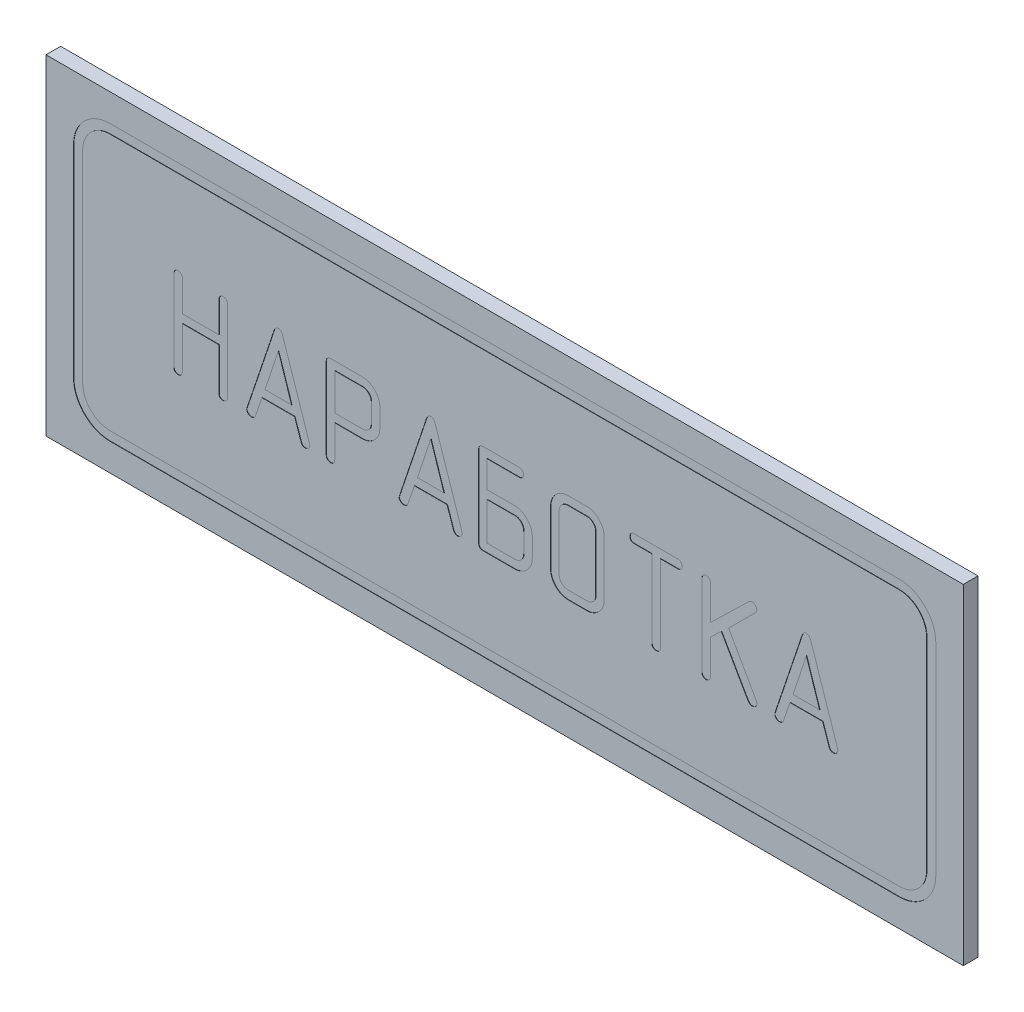
SolidWorks part; units mm, degrees
ref_plane "Спереди" through (0, 0, 0) normal (0, 0, 1) x (1, 0, 0)
ref_plane "Сверху" through (0, 0, 0) normal (0, 1, 0) x (1, 0, 0)
ref_plane "Справа" through (0, 0, 0) normal (1, 0, 0) x (0, 0, -1)
sketch "Эскиз1" plane through (0, 0, 0) normal (0, 0, 1) x (1, 0, 0)
  line L1 (0, 0) -> (50, 0)
  line L2 (0, 0) -> (0, 18)
  line L3 (0, 18) -> (50, 18)
  line L4 (50, 0) -> (50, 18)
  dimension "D1" = 50
  dimension "D2" = 18
extrude "Вытянуть1" add sketch "Эскиз1" along normal blind 0.8
sketch "Эскиз2" plane through (0, 0, 0.8) normal (0, 0, 1) x (1, 0, 0)
  line L0 (0, 0) -> (50, 0) construction
  line L1 (0, 18) -> (0, 0) construction
  text T0 "НАРАБОТКА" font "GOST type B" height 5
  dimension "D1" = 6.5
  dimension "D2" = 6.5
extrude "Вырез-Вытянуть1" cut sketch "Эскиз2" against normal blind 0.02
sketch "Эскиз3" plane through (0, 0, 0.8) normal (0, 0, 1) x (1, 0, 0)
  line L0 (50, 18) -> (0, 18) construction
  line L1 (3.5, 2) -> (46.5, 2)
  line L2 (2, 3.5) -> (2, 14.5)
  line L3 (3.5, 16) -> (46.5, 16)
  line L4 (48, 3.5) -> (48, 14.5)
  line L5 (0, 0) -> (50, 0) construction
  line L6 (0, 18) -> (0, 0) construction
  line L7 (50, 0) -> (50, 18) construction
  arc A0 (2, 14.5) -> (3.5, 16) centre (3.5, 14.5) cw
  arc A1 (46.5, 16) -> (48, 14.5) centre (46.5, 14.5) cw
  arc A2 (46.5, 2) -> (48, 3.5) centre (46.5, 3.5) ccw
  arc A3 (3.5, 2) -> (2, 3.5) centre (3.5, 3.5) cw
  dimension "D5" = 1.5
  dimension "D1" = 2
  dimension "D2" = 2
  dimension "D3" = 2
  dimension "D4" = 2
extrude "Вырез-Вытянуть-Тонкостенный1" cut sketch "Эскиз3" against normal blind 0.02 and the other way blind 0.02 thin thin type one direction wall 0.5
